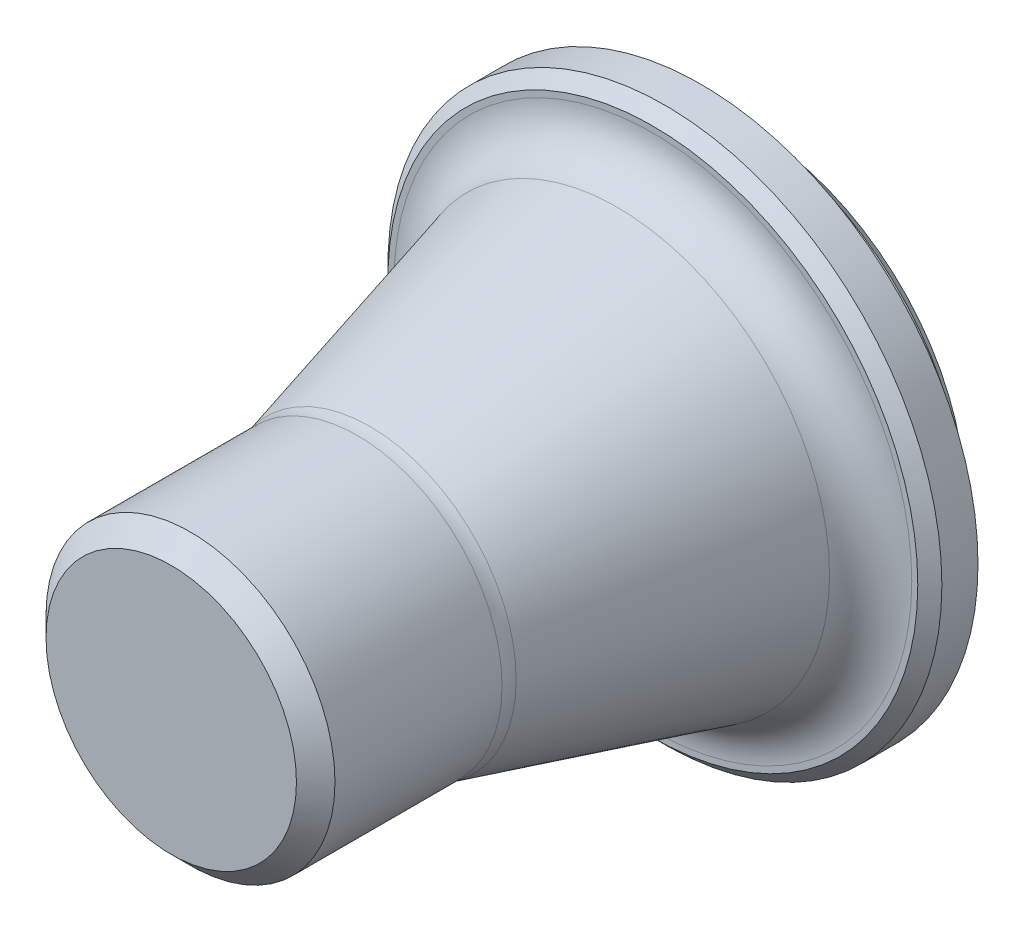
SolidWorks part; units mm, degrees
material "PET"
ref_plane "Front Plane" through (0, 0, 0) normal (0, 0, 1) x (1, 0, 0)
ref_plane "Top Plane" through (0, 0, 0) normal (0, 1, 0) x (1, 0, 0)
ref_plane "Right Plane" through (0, 0, 0) normal (1, 0, 0) x (0, 0, -1)
sketch "Sketch1" plane through (0, 0, 0) normal (0, 0, 1) x (1, 0, 0)
  circle A2 centre (0, 0) radius 30.0863
  circle A3 centre (0, 0) radius 30.0863
  dimension "D1" = 1.27
extrude "Boss-Extrude1" add sketch "Sketch1" against normal blind 95.25
sketch "Sketch2" plane through (0, 0, 0) normal (0, 0, 1) x (1, 0, 0)
  circle A0 centre (0, 0) radius 36.5125 construction
  circle A1 centre (0, 0) radius 36.5125
extrude "Boss-Extrude2" add sketch "Sketch2" along normal blind 25.4 and the other way offset from surface 6.35 other way up to face at (30.0863, 0, -95.25)
sketch "Sketch3" plane through (0, 0, 25.4) normal (0, 0, 1) x (1, 0, 0)
  circle A0 centre (0, 0) radius 19.05
  dimension "D1" = 38.1
extrude "Boss-Extrude3" add sketch "Sketch3" along normal blind 38.1
draft "Draft1" type of draft neutral plane draft angle 15 faces to draft 1 face at (19.05, 0, 63.5) neutral plane through (0, 0, 63.5) neutral plane normal (0, 0, 1) parameters "D1"=15
sketch "Sketch4" plane through (0, 0, 63.5) normal (0, 0, 1) x (1, 0, 0)
  circle A1 centre (0, 0) radius 19.05
  circle A2 centre (0, 0) radius 19.05
  dimension "D1" = 0
extrude "Boss-Extrude4" add sketch "Sketch4" along normal blind 25.4
chamfer "Chamfer1" distance 2.54 angle 45 1 edges at (19.05, 0, 88.9)
fillet "Fillet1" radius 6.35 2 edges at (29.2589, 0, 25.4) (19.05, 0, 63.5)
chamfer "Chamfer2" distance 1.5875 angle 45 1 edges at (36.5125, 0, 25.4)
sketch "Sketch5" plane through (0, 0, -95.25) normal (0, 0, -1) x (-1, 0, 0)
  circle A0 centre (0, 0) radius 26.9113
  circle A1 centre (0, 0) radius 30.0863 construction
  dimension "D1" = 3.175
extrude "Cut-Extrude1" cut sketch "Sketch5" against normal up to surface (120.65 mm away) up to face at (34.925, 0, 25.4)
sketch "Sketch6" plane through (0, 0, 25.4) normal (0, 0, -1) x (-1, 0, 0)
  circle A0 centre (0, 0) radius 15.875
  circle A1 centre (0, 0) radius 19.05 construction
  circle A2 centre (0, 0) radius 16.51 construction
  dimension "D1" = 3.175
extrude "Cut-Extrude2" cut sketch "Sketch6" against normal offset from surface (60.325 mm away) 3.175 up to face at (16.51, 0, 88.9)
sketch "Sketch9" plane through (0, 0, -95.25) normal (0, 0, -1) x (-1, 0, 0)
  line L0 (-17.3073, -1.0596) -> (-37.8448, 0.9697)
  line L1 (-37.8448, 0.9697) -> (-33.9423, 40.4648)
  line L2 (-33.9423, 40.4648) -> (-13.4048, 38.4355)
  line L3 (-13.4048, 38.4355) -> (-17.3073, -1.0596)
extrude "Cut-Extrude3" [suppressed] cut sketch "Sketch9" against normal blind 61.595
sketch "Sketch11" plane through (0, 0, -95.25) normal (0, 0, -1) x (-1, 0, 0)
  circle A0 centre (0, 0) radius 36.5125 construction
  circle A1 centre (0, 0) radius 36.5125
extrude "Cut-Extrude4" cut sketch "Sketch11" against normal blind 114.3
sketch "Sketch13" plane through (0, 0, 19.05) normal (0, 0, -1) x (-1, 0, 0)
  circle A0 centre (0, 0) radius 26.9113 construction
  circle A1 centre (0, 0) radius 26.9113
  circle A2 centre (0, 0) radius 30.0863
  dimension "D1" = 60.1726
extrude "Boss-Extrude5" add sketch "Sketch13" along normal blind 6.35
chamfer "Chamfer3" distance 1.5875 angle 45 1 edges at (-30.0863, 0, 12.7)
